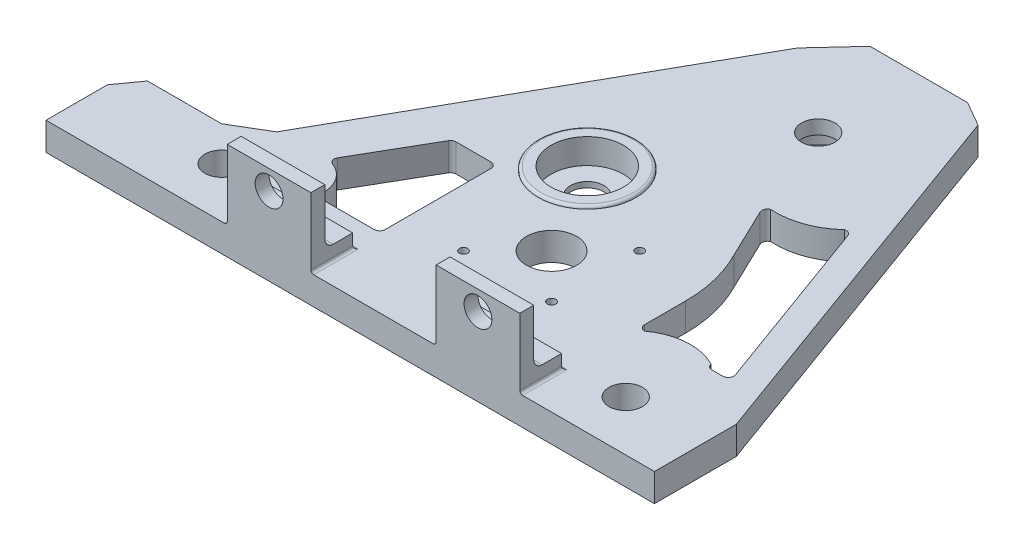
SolidWorks part; units mm, degrees
ref_plane "Alzado" through (0, 0, 0) normal (0, 0, 1) x (1, 0, 0)
ref_plane "Planta" through (0, 0, 0) normal (0, 1, 0) x (1, 0, 0)
ref_plane "Vista lateral" through (0, 0, 0) normal (1, 0, 0) x (0, 0, -1)
sketch "Croquis1" plane through (0, 0, 0) normal (0, 1, 0) x (1, 0, 0)
  line L0 (-109.095, 0) -> (109.095, 0)
  line L1 (-109.095, 0) -> (-109.095, 22)
  line L2 (-109.095, 22) -> (-103.085, 30.39)
  line L3 (-103.085, 30.39) -> (-76.4898, 30.39)
  line L4 (-76.4898, 30.39) -> (-64.095, 37.77)
  line L5 (-64.095, 37.77) -> (3.225, 157.21)
  line L6 (3.225, 157.21) -> (15.6978, 170.7122)
  line L7 (15.6978, 170.7122) -> (50.6978, 170.7122)
  line L8 (50.6978, 170.7122) -> (59.5004, 165.63)
  line L9 (59.5004, 165.63) -> (109.095, 29.37)
  line L10 (109.095, 29.37) -> (109.095, 0)
  line L11 (-34.9592, 24.9055) -> (-16.3292, 24.9055)
  line L12 (-14.3292, 26.9055) -> (-14.3292, 64.8055)
  line L13 (-16.3292, 66.8055) -> (-28.8645, 66.8055)
  line L14 (-30.5966, 65.8055) -> (-45.1245, 40.6425)
  line L15 (-36.9592, 26.9055) -> (-36.9592, 27.4711)
  line L16 (70.5188, 107.9281) -> (93.5924, 44.534)
  line L17 (91.713, 41.85) -> (87.8539, 41.85)
  line L24 (61.7193, 43.85) -> (61.7193, 58.5)
  line L26 (56.1328, 81.4661) -> (47.4697, 99.5151)
  circle A0 centre (33.1978, 134.63) radius 13
  circle A1 centre (33.1978, 134.63) radius 6
  circle A2 centre (3.225, 81.78) radius 13
  circle A3 centre (3.225, 81.78) radius 6
  circle A4 centre (-64.095, 18) radius 6
  circle A5 centre (80.805, 18) radius 6
  circle A6 centre (22.115, 50.09) radius 9
  circle A7 centre (37.905, 65.88) radius 1.5
  circle A8 centre (37.905, 34.3) radius 1.5
  circle A9 centre (6.325, 34.3) radius 1.5
  arc A11 (-36.9592, 27.4711) -> (-44.095, 37.77) centre (-47.9592, 27.4711) ccw
  arc A12 (-16.3292, 24.9055) -> (-14.3292, 26.9055) centre (-16.3292, 26.9055) ccw
  arc A13 (-34.9592, 24.9055) -> (-36.9592, 26.9055) centre (-34.9592, 26.9055) cw
  arc A14 (-44.095, 37.77) -> (-45.1245, 40.6425) centre (-43.3924, 39.6425) cw
  arc A15 (-14.3292, 64.8055) -> (-16.3292, 66.8055) centre (-16.3292, 64.8055) ccw
  arc A16 (-30.5966, 65.8055) -> (-28.8645, 66.8055) centre (-28.8645, 64.8055) cw
  arc A20 (91.713, 41.85) -> (93.5924, 44.534) centre (91.713, 43.85) ccw
  arc A22 (61.7193, 58.5) -> (56.1328, 81.4661) centre (11.7193, 58.5) ccw
  arc A24 (87.8539, 41.85) -> (85.8794, 43.5319) centre (87.8539, 43.85) cw
  arc A25 (63.7193, 41.85) -> (61.7193, 43.85) centre (63.7193, 43.85) cw
  arc A26 (70.5188, 107.9281) -> (68.0232, 109.1468) centre (68.6395, 107.2441) ccw
  arc A29 (63.7193, 41.85) -> (85.8794, 43.5319) centre (76.1479, 24.9228) cw
  arc A31 (47.4697, 99.5151) -> (48.5533, 102.2467) centre (49.2727, 100.3805) cw
  arc A32 (48.5533, 102.2467) -> (68.0232, 109.1468) centre (50.3012, 128.2338) ccw
  point P4 (0, 0)
  point P16 (33.1978, 170.7122)
  point P41 (-14.3292, 24.9055)
  point P44 (-36.9592, 24.9055)
  point P47 (-46.4391, 38.3655)
  point P50 (-14.3292, 66.8055)
  point P53 (-30.0192, 66.8055)
  point P65 (61.7193, 58.4)
  point P66 (94.5693, 41.85)
  point P68 (46.5352, 101.462)
  point P74 (61.7193, 41.85)
  point P77 (69.0251, 112.0322)
  point P80 (45.1703, 104.3057)
  dimension "D17" = 26
  dimension "D18" = 12
  dimension "D25" = 12
  dimension "D26" = 12
  dimension "D28" = 18
  dimension "D30" = 3
  dimension "D31" = 3
  dimension "D32" = 3
  dimension "D37" = 60
  dimension "D40" = 11
  dimension "D44" = 2
  dimension "D45" = 50
  dimension "D49" = 16.65
  dimension "D48" = 2
  dimension "D52" = 14.65
  dimension "D54" = 2
  dimension "D55" = 21
  dimension "D57" = 26.0458
  dimension "D59" = 107.9281
  dimension "D60" = 109.1468
  dimension "D62" = 43.5319
  dimension "D64" = 14.4286
  dimension "D46" = 2
  dimension "D68" = 33.9178
  dimension "D69" = 31.9503
  dimension "D70" = 31.9653
  dimension "D1" = 218.19
  dimension "D2" = 22
  dimension "D3" = 6.01
  dimension "D4" = 30.39
  dimension "D5" = 37.77
  dimension "D6" = 30.77
  dimension "D7" = 157.21
  dimension "D8" = 132.731
  dimension "D9" = 150
  dimension "D10" = 112.32
  dimension "D11" = 35
  dimension "D12" = 29.37
  dimension "D13" = 165.63
  dimension "D14" = 110
  dimension "D15" = 45
  dimension "D16" = 134.63
  dimension "D19" = 36.0822
  dimension "D20" = 112.32
  dimension "D21" = 81.78
  dimension "D22" = 45
  dimension "D23" = 18
  dimension "D24" = 28.29
  dimension "D27" = 131.21
  dimension "D29" = 50.09
  dimension "D33" = 31.58
  dimension "D34" = 15.79
  dimension "D35" = 34.3
  dimension "D36" = 31.58
  dimension "D38" = 22.63
  dimension "D39" = 15.69
  dimension "D41" = 41.9
  dimension "D42" = 28.44
  dimension "D43" = 65
  dimension "D47" = 32.85
  dimension "D50" = 71.83
  dimension "D51" = 41.85
  dimension "D53" = 24.84
  dimension "D56" = 5.64
  dimension "D58" = 22.18
  dimension "D61" = 12.0653
  dimension "D63" = 16.9719
  dimension "D65" = 23.0999
  dimension "D66" = 5.64
  dimension "D67" = 5.64
extrude "Saliente-Extruir1" add sketch "Croquis1" along normal blind 10 contours L10 L9 L8 L7 L6 L5 L4 L3 L2 L1 L0 A29 A25 L24 A22 L26 A26 L16 A20 L17 A24 A9 A8 A7 A6 A5 A4 A2 A0 L14 A16 L13 A15 L12 A12 L11 A13 L15 A11 region at (16.2293, 0, -64.1925)
sketch "Croquis2" plane through (0, 10, 0) normal (0, 1, 0) x (1, 0, 0)
  line L0 (-109.095, 0) -> (109.095, 0) construction
  line L1 (-44.095, 15) -> (-14.095, 15)
  line L2 (-44.095, 15) -> (-44.095, 0)
  line L3 (-44.095, 0) -> (-14.095, 0)
  line L4 (-14.095, 15) -> (-14.095, 0)
  line L5 (-44.095, 15) -> (-14.095, 0) construction
  line L6 (-44.095, 0) -> (-14.095, 15) construction
  line L7 (30.805, 15) -> (60.805, 15)
  line L8 (30.805, 15) -> (30.805, 0)
  line L9 (30.805, 0) -> (60.805, 0)
  line L10 (60.805, 15) -> (60.805, 0)
  line L11 (30.805, 15) -> (60.805, 0) construction
  line L12 (30.805, 0) -> (60.805, 15) construction
  line L13 (-109.095, 0) -> (-109.095, 22) construction
  point P0 (-29.095, 7.5)
  point P5 (45.805, 7.5)
  dimension "D1" = 15
  dimension "D2" = 0
  dimension "D3" = 0
  dimension "D4" = 15
  dimension "D5" = 65
  dimension "D6" = 30
  dimension "D7" = 30
  dimension "D8" = 48.29
extrude "Saliente-Extruir2" add sketch "Croquis2" along normal blind 5
ref_plane "Plano1" through (0, 15, 0) normal (0, 1, 0) x (1, 0, 0)
sketch "Croquis3" plane through (0, 15, 0) normal (0, 1, 0) x (1, 0, 0)
  line L0 (-44.095, 15) -> (-44.095, 0) construction
  line L1 (-44.095, 5) -> (-14.095, 5)
  line L2 (-44.095, 5) -> (-44.095, 0)
  line L3 (-44.095, 0) -> (-14.095, 0)
  line L4 (-14.095, 5) -> (-14.095, 0)
  line L5 (-44.095, 0) -> (-14.095, 0) construction
  line L6 (30.805, 15) -> (30.805, 0) construction
  line L7 (30.805, 5) -> (60.805, 5)
  line L8 (30.805, 5) -> (30.805, 0)
  line L9 (30.805, 0) -> (60.805, 0)
  line L10 (60.805, 5) -> (60.805, 0)
  line L11 (30.805, 0) -> (60.805, 0) construction
  line L13 (109.095, 29.37) -> (109.095, 0) construction
  dimension "D1" = 5
  dimension "D2" = 5
  dimension "D3" = 48.29
  dimension "D4" = 123.19
extrude "Saliente-Extruir3" add sketch "Croquis3" along normal blind 20
ref_plane "Plano2" through (0, 0, -5) normal (0, 0, -1) x (-1, 0, 0)
sketch "Croquis4" plane through (0, 0, -5) normal (0, 0, -1) x (-1, 0, 0)
  line L0 (-30.805, 35) -> (-30.805, 15) construction
  line L1 (44.095, 35) -> (44.095, 15) construction
  line L2 (-60.805, 35) -> (-30.805, 35) construction
  line L3 (14.095, 35) -> (44.095, 35) construction
  circle A0 centre (-45.805, 28) radius 5
  circle A1 centre (29.095, 28) radius 5
  dimension "D1" = 10
  dimension "D2" = 10
  dimension "D3" = 15
  dimension "D4" = 15
  dimension "D5" = 7
  dimension "D6" = 7
extrude "Cortar-Extruir1" cut sketch "Croquis4" against normal blind 20
fillet "Redondeo1" radius 1 4 edges at (60.805, 10, -7.5) (-14.095, 10, -7.5) (30.805, 10, -7.5) (-44.095, 10, -7.5)
fillet "Redondeo2" radius 1 2 edges at (45.805, 10, -15) (-29.095, 10, -15)
fillet "Redondeo3" radius 3 2 edges at (45.805, 15, -5) (-29.095, 15, -5)
sketch "Croquis6" plane through (0, 10, 0) normal (0, 1, 0) x (1, 0, 0)
  line L19 (29.805, 0) -> (29.805, 16)
  line L20 (29.805, 16) -> (61.805, 16)
  line L21 (61.805, 16) -> (61.805, 0)
  line L22 (61.805, 0) -> (109.095, 0)
  line L23 (109.095, 0) -> (109.095, 29.37)
  line L24 (109.095, 29.37) -> (59.5004, 165.63)
  line L25 (59.5004, 165.63) -> (50.6978, 170.7122)
  line L26 (50.6978, 170.7122) -> (15.6978, 170.7122)
  line L27 (15.6978, 170.7122) -> (3.225, 157.21)
  line L28 (3.225, 157.21) -> (-64.095, 37.77)
  line L29 (-64.095, 37.77) -> (-76.4898, 30.39)
  line L30 (-76.4898, 30.39) -> (-103.085, 30.39)
  line L31 (-103.085, 30.39) -> (-109.095, 22)
  line L32 (-109.095, 22) -> (-109.095, 0)
  line L33 (-109.095, 0) -> (-45.095, 0)
  line L34 (-45.095, 0) -> (-45.095, 16)
  line L35 (-45.095, 16) -> (-13.095, 16)
  line L36 (-13.095, 16) -> (-13.095, 0)
  line L37 (-13.095, 0) -> (29.805, 0)
  line L38 (29.805, 0) -> (29.805, 16)
  line L39 (29.805, 16) -> (61.805, 16)
  line L40 (61.805, 16) -> (61.805, 0)
  line L41 (61.805, 0) -> (109.095, 0)
  line L42 (109.095, 0) -> (109.095, 29.37)
  line L43 (109.095, 29.37) -> (59.5004, 165.63)
  line L44 (59.5004, 165.63) -> (50.6978, 170.7122)
  line L45 (50.6978, 170.7122) -> (15.6978, 170.7122)
  line L46 (15.6978, 170.7122) -> (3.225, 157.21)
  line L47 (3.225, 157.21) -> (-64.095, 37.77)
  line L48 (-64.095, 37.77) -> (-76.4898, 30.39)
  line L49 (-76.4898, 30.39) -> (-103.085, 30.39)
  line L50 (-103.085, 30.39) -> (-109.095, 22)
  line L51 (-109.095, 22) -> (-109.095, 0)
  line L52 (-109.095, 0) -> (-45.095, 0)
  line L53 (-45.095, 0) -> (-45.095, 16)
  line L54 (-45.095, 16) -> (-13.095, 16)
  line L55 (-13.095, 16) -> (-13.095, 0)
  line L56 (-13.095, 0) -> (29.805, 0)
  circle A0 centre (33.1978, 134.63) radius 13
  circle A1 centre (33.1978, 134.63) radius 6
  circle M27 centre (33.1978, 134.63) radius 13
  dimension "D2" = 12
  dimension "D3" = 26
  dimension "D1" = 0
extrude "Saliente-Extruir4" add sketch "Croquis6" against normal blind 5 contours A1 M27 region at (20.5655, 10, -134.63)
sketch "Croquis7" plane through (0, 0, 0) normal (0, -1, 0) x (1, 0, 0)
  circle A0 centre (33.1978, -134.63) radius 20
  circle A1 centre (33.1978, -134.63) radius 13
  dimension "D1" = 40
  dimension "D2" = 26
extrude "Saliente-Extruir6" add sketch "Croquis7" along normal blind 3 separate body
fillet "Redondeo5" radius 3 1 edges at (33.1978, -3, -154.63)
sketch "Croquis8" plane through (0, 0, 0) normal (0, -1, 0) x (1, 0, 0)
  circle A0 centre (3.225, -81.78) radius 13
  circle A1 centre (3.225, -81.78) radius 6
  dimension "D1" = 12
  dimension "D2" = 26
extrude "Saliente-Extruir7" add sketch "Croquis8" against normal blind 2
sketch "Croquis9" plane through (0, 10, 0) normal (0, 1, 0) x (1, 0, 0)
  circle A1 centre (3.225, 81.78) radius 17.5
  circle A2 centre (3.225, 81.78) radius 13
  dimension "D1" = 35
  dimension "D2" = 26
extrude "Saliente-Extruir8" add sketch "Croquis9" along normal blind 1
fillet "Redondeo6" radius 1 1 edges at (3.225, 11, -64.28)
